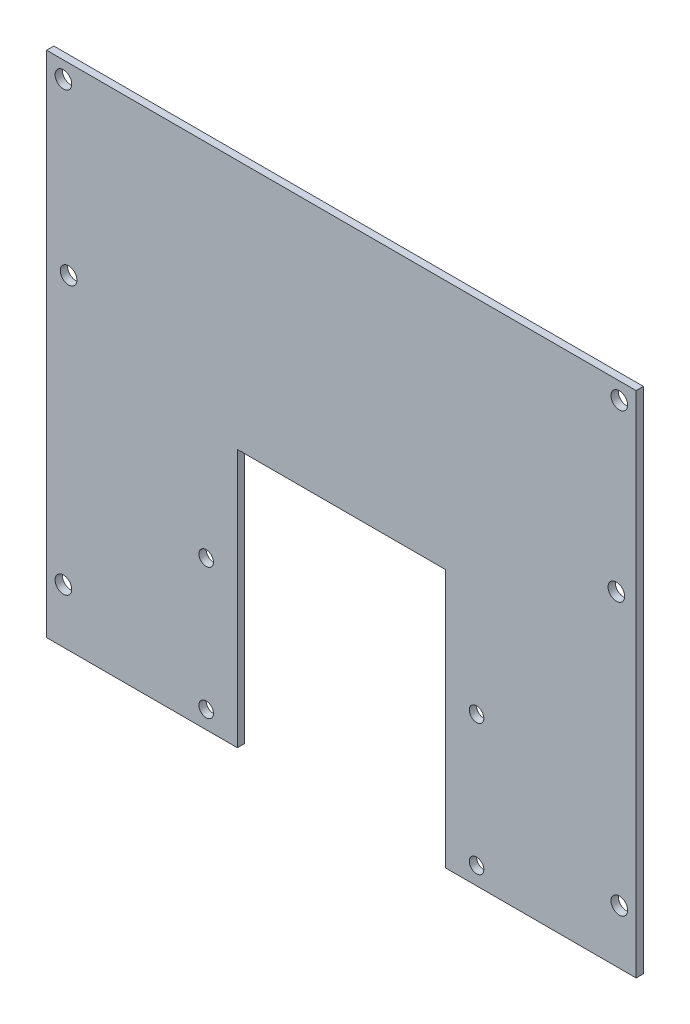
SolidWorks part; units mm, degrees
material "Plain Carbon Steel"
ref_plane "Front Plane" through (0, 0, 0) normal (0, 0, 1) x (1, 0, 0)
ref_plane "Top Plane" through (0, 0, 0) normal (0, 1, 0) x (1, 0, 0)
ref_plane "Right Plane" through (0, 0, 0) normal (1, 0, 0) x (0, 0, -1)
sketch "Sketch1" plane through (0, 0, 0) normal (0, 0, 1) x (1, 0, 0)
  line L0 (-54.2366, -134.5978) -> (-54.2366, -10.3612)
  line L1 (-145.9732, 110) -> (137.5, 110)
  line L2 (-145.9732, 110) -> (-145.9732, -134.5978)
  line L3 (-145.9732, -134.5978) -> (-54.2366, -134.5978)
  line L4 (137.5, 110) -> (137.5, -134.5978)
  line L5 (-145.9732, 110) -> (137.5, -134.5978) construction
  line L6 (-145.9732, -134.5978) -> (137.5, 110) construction
  line L7 (-54.2366, -10.3612) -> (45.7634, -10.3612)
  line L8 (45.7634, -10.3612) -> (45.7634, -134.5978)
  line L9 (45.7634, -134.5978) -> (137.5, -134.5978)
  point P0 (-4.2366, -12.2989)
  dimension "D1" = 283.4732
  dimension "D2" = 244.5978
  dimension "D3" = 100
  dimension "D4" = 124.2366
  dimension "D5" = 91.7366
base flange "Base-Flange1" sketch "Sketch1" thickness 3.5 reverse thickness direction no parameters "D1"=0.7366
sketch "Sketch2" plane through (0, 0, -3.5) normal (0, 0, -1) x (-1, 0, 0)
  line L0 (-45.7634, -134.5978) -> (-137.5, -134.5978) construction
  line L1 (-45.7634, -10.3612) -> (-45.7634, -134.5978) construction
  line L3 (54.2366, -134.5978) -> (54.2366, -10.3612) construction
  circle A0 centre (-60.7634, -126.0978) radius 3.5
  circle A1 centre (69.2366, -126.0978) radius 3.5
  circle A2 centre (-60.7634, -63.0978) radius 3.5
  circle A3 centre (69.2366, -63.0978) radius 3.5
  dimension "D2" = 15
  dimension "D3" = 15
  dimension "D4" = 63
  dimension "D1" = 8.5
extrude "Cut-Extrude1" cut sketch "Sketch2" against normal up to surface (3.5 mm away) normal cut yes up to face at (-4.2366, -42.3892, 0)
sketch "Sketch3" plane through (0, 0, -3.5) normal (0, 0, -1) x (-1, 0, 0)
  line L0 (-137.5, 110) -> (145.9732, 110) construction
  line L1 (145.9732, 110) -> (145.9732, -134.5978) construction
  line L2 (-137.5, -134.5978) -> (-137.5, 110) construction
  line L3 (-45.7634, -134.5978) -> (-137.5, -134.5978) construction
  line L4 (145.9732, -134.5978) -> (54.2366, -134.5978) construction
  circle A0 centre (137.8732, 101.9) radius 4
  circle A1 centre (-129.4, 101.9) radius 4
  circle A2 centre (-129.4, -108.4732) radius 4
  circle A3 centre (137.8732, -108.4732) radius 4
  dimension "D3" = 8.1
  dimension "D5" = 8.1
  dimension "D7" = 26.1246
  dimension "D1" = 8.1
  dimension "D2" = 8.1
  dimension "D4" = 8.1
  dimension "D6" = 26.1246
  dimension "D8" = 8.1
extrude "Cut-Extrude2" cut sketch "Sketch3" against normal up to surface (3.5 mm away) normal cut yes up to face at (-72.7366, -126.0978, 0)
hole_wizard "Ø8.0mm Dowel Hole1" positions "Sketch4" profile "Sketch5" hole size "Ø8.0" standard "ANSI Metric" end condition through all
sketch "Sketch4" plane through (-128.3161, 74.6247, 0) normal (0, 0, 1) x (1, 0, 0)
  point P0 (256.2933, -53.0924)
sketch "Sketch5" plane through (127.9772, 21.5323, 0) normal (1, 0, 0) x (0, -1, 0)
  line L0 (0, 0) -> (0, 3.5)
  line L1 (0, 3.5) -> (4, 3.5)
  line L2 (4, 3.5) -> (4, 0)
  line L3 (4, 0) -> (0, 0)
  line L4 (0, -6.35) -> (0, 107.95) construction
  dimension "Thru Hole Dia." = 8
  dimension "Thru Hole Depth" = 3.5
hole_wizard "Ø8.0mm Dowel Hole2" positions "Sketch6" profile "Sketch7" hole size "Ø8.0" standard "ANSI Metric" end condition through all
sketch "Sketch6" plane through (-128.3161, 74.6247, 0) normal (0, 0, 1) x (1, 0, 0)
  point P0 (-7.0724, -53.0924)
sketch "Sketch7" plane through (-135.3885, 21.5323, 0) normal (1, 0, 0) x (0, -1, 0)
  line L0 (0, 0) -> (0, 3.5)
  line L1 (0, 3.5) -> (4, 3.5)
  line L2 (4, 3.5) -> (4, 0)
  line L3 (4, 0) -> (0, 0)
  line L4 (0, -6.35) -> (0, 107.95) construction
  dimension "Thru Hole Dia." = 8
  dimension "Thru Hole Depth" = 3.5
sketch "Bend-Lines1" [suppressed] plane through (0, 0, 0) normal (0, 1, 0) x (1, 0, 0)
sketch "Bounding-Box1" [suppressed] plane through (0, 0, 0) normal (0, 1, 0) x (1, 0, 0)
sheet metal parameters "Sheet-Metal1" thickness 3.5 parameters "D1"=0.7366
flat pattern "Flat-Pattern1" [suppressed]
sketch "Bend-Lines2" plane through (0, 0, 0) normal (0, 1, 0) x (1, 0, 0)
sketch3d "Bounding-Box2" [suppressed]
  line L0 (-145.9732, -134.5978, 0) -> (137.5, -134.5978, 0) construction
  line L1 (-145.9732, 110, 0) -> (137.5, 110, 0) construction
  line L2 (-145.9732, -134.5978, 0) -> (-145.9732, 110, 0) construction
  line L3 (137.5, -134.5978, 0) -> (137.5, 110, 0) construction
sheet metal parameters "Sheet-Metal2" thickness 3.5 parameters "D1"=0.7366
flat pattern "Flat-Pattern1"
sketch "Bend-Lines2" plane through (0, 0, 0) normal (0, 1, 0) x (1, 0, 0)
sketch3d "Bounding-Box2" [suppressed]
  line L0 (-145.9732, -134.5978, 0) -> (137.5, -134.5978, 0) construction
  line L1 (-145.9732, 110, 0) -> (137.5, 110, 0) construction
  line L2 (-145.9732, -134.5978, 0) -> (-145.9732, 110, 0) construction
  line L3 (137.5, -134.5978, 0) -> (137.5, 110, 0) construction
sheet metal parameters "Sheet-Metal3" thickness 3.5 parameters "D1"=0.7366
flat pattern "Flat-Pattern1"
sketch "Bend-Lines2" plane through (0, 0, 0) normal (0, 1, 0) x (1, 0, 0)
sketch3d "Bounding-Box2" [suppressed]
  line L0 (-145.9732, -134.5978, 0) -> (137.5, -134.5978, 0) construction
  line L1 (-145.9732, 110, 0) -> (137.5, 110, 0) construction
  line L2 (-145.9732, -134.5978, 0) -> (-145.9732, 110, 0) construction
  line L3 (137.5, -134.5978, 0) -> (137.5, 110, 0) construction
sheet metal parameters "Sheet-Metal4" thickness 3.5 parameters "D1"=0.7366
flat pattern "Flat-Pattern1"
sketch "Bend-Lines2" plane through (0, 0, 0) normal (0, 1, 0) x (1, 0, 0)
sketch3d "Bounding-Box2" [suppressed]
  line L0 (-145.9732, -134.5978, 0) -> (137.5, -134.5978, 0) construction
  line L1 (-145.9732, 110, 0) -> (137.5, 110, 0) construction
  line L2 (-145.9732, -134.5978, 0) -> (-145.9732, 110, 0) construction
  line L3 (137.5, -134.5978, 0) -> (137.5, 110, 0) construction
sheet metal parameters "Sheet-Metal5" thickness 3.5 parameters "D1"=0.7366
flat pattern "Flat-Pattern1"
sketch "Bend-Lines2" plane through (0, 0, 0) normal (0, 1, 0) x (1, 0, 0)
sketch3d "Bounding-Box2" [suppressed]
  line L0 (-145.9732, -134.5978, 0) -> (137.5, -134.5978, 0) construction
  line L1 (-145.9732, 110, 0) -> (137.5, 110, 0) construction
  line L2 (-145.9732, -134.5978, 0) -> (-145.9732, 110, 0) construction
  line L3 (137.5, -134.5978, 0) -> (137.5, 110, 0) construction
